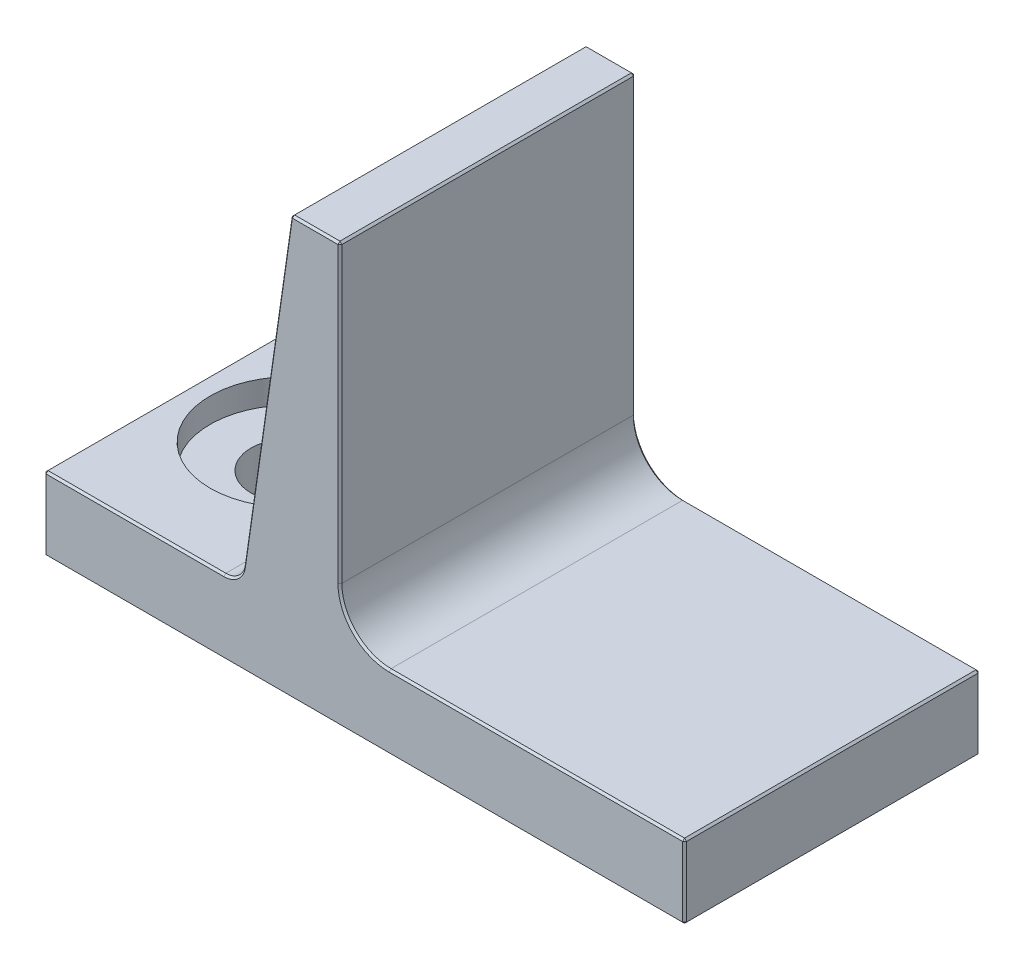
SolidWorks part; units mm, degrees
ref_plane "Front Plane" through (0, 0, 0) normal (0, 0, 1) x (1, 0, 0)
ref_plane "Top Plane" through (0, 0, 0) normal (0, 1, 0) x (1, 0, 0)
ref_plane "Right Plane" through (0, 0, 0) normal (1, 0, 0) x (0, 0, -1)
sketch "Sketch1" plane through (0, 0, 0) normal (0, 0, 1) x (1, 0, 0)
  line L0 (0, 0) -> (44.45, 0)
  line L1 (44.45, 0) -> (44.45, -9.525)
  line L2 (44.45, -9.525) -> (-38.1608, -9.525)
  line L3 (-38.1608, -9.525) -> (-38.1608, 0)
  line L4 (-38.1608, 0) -> (-12.7608, 0)
  line L5 (-12.7608, 0) -> (-6.35, 44.45)
  line L6 (-6.35, 44.45) -> (0, 44.45)
  line L7 (0, 44.45) -> (0, 0)
  point P5 (-45.212, -12.7)
  point P10 (-45.212, -12.2834)
  dimension "D1" = 44.45
  dimension "D2" = 44.45
  dimension "D3" = 9.525
  dimension "D4" = 38.1608
  dimension "D5" = 6.35
  dimension "D6" = 25.4
extrude "Boss-Extrude1" add sketch "Sketch1" along normal blind 38.1
hole_wizard "CBORE for 3/8 Binding Head Machine Screw1" positions "Sketch6" profile "Sketch3" counterbore size "3/8" standard "ANSI Inch" end condition through all
sketch "Sketch6" plane through (0, 0, 0) normal (0, 1, 0) x (1, 0, 0)
  line L0 (-12.7608, 0) -> (-38.1608, 0) construction
  line L1 (-38.1608, -38.1) -> (-38.1608, 0) construction
  point P0 (-25.4608, -19.05)
  point P5 (-25.4608, 0)
  point P8 (-38.1608, -19.05)
sketch "Sketch3" plane through (-25.4608, 0, 19.05) normal (1, 0, 0) x (0, 0, 1)
  line L0 (0, 0) -> (0, 9.525)
  line L1 (0, 9.525) -> (5.0419, 9.525)
  line L3 (5.0419, 9.525) -> (5.0419, 3.175)
  line L4 (10.3187, 3.175) -> (5.0419, 3.175)
  line L5 (10.3187, 3.175) -> (10.3187, 0)
  line L7 (10.3187, 0) -> (0, 0)
  line L11 (0, 0) -> (0, 107.95) construction
  dimension "Thru Hole Dia." = 10.0838
  dimension "Thru Hole Depth" = 9.525
  dimension "C'Bore Depth" = 3.175
fillet "Fillet1" radius 2.54 1 edges at (-12.7608, 0, 19.05)
fillet "Fillet2" radius 6.35 1 edges at (0, 0, 19.05)
chamfer "Chamfer1" distance 0.254 angle 45 26 edges at (-6.35, 44.45, 19.05) (-3.175, 44.45, 0) (-9.3984, 23.3137, 0) (-13.2978, 0.62, 0) (-26.5608, 0, 0) (-38.1608, -4.7625, 0) (3.1446, -9.525, 0) (44.45, -4.7625, 0) (25.4, 0, 0) (1.8599, 1.8599, 0) (0, 25.4, 0) (44.45, -4.7625, 38.1) (44.45, -9.525, 19.05) (3.1446, -9.525, 38.1) (-38.1608, -9.525, 19.05) (-38.1608, -4.7625, 38.1) (-38.1608, 0, 19.05) (-26.5608, 0, 38.1) (-13.2978, 0.62, 38.1) (-9.3984, 23.3137, 38.1) (-3.175, 44.45, 38.1) (0, 44.45, 19.05) (0, 25.4, 38.1) (1.8599, 1.8599, 38.1) (25.4, 0, 38.1) (44.45, 0, 19.05) first distance on face at (-3.175, 44.45, 19.05) first distance on face at (-9.3984, 23.3137, 19.05) first distance on face at (-13.5008, 0.8544, 19.05) first distance on face at (-25.4608, 0, 29.3687) first distance on face at (-38.1608, -4.7625, 19.05) first distance on face at (-25.4608, -9.525, 24.0919) first distance on face at (44.45, -4.7625, 19.05) first distance on face at (-1.5738, 7.6594, 0) first distance on face at (2.5174, 2.5174, 19.05) first distance on face at (0, 25.4, 19.05) first distance on face at (-1.5738, 7.6594, 38.1)
